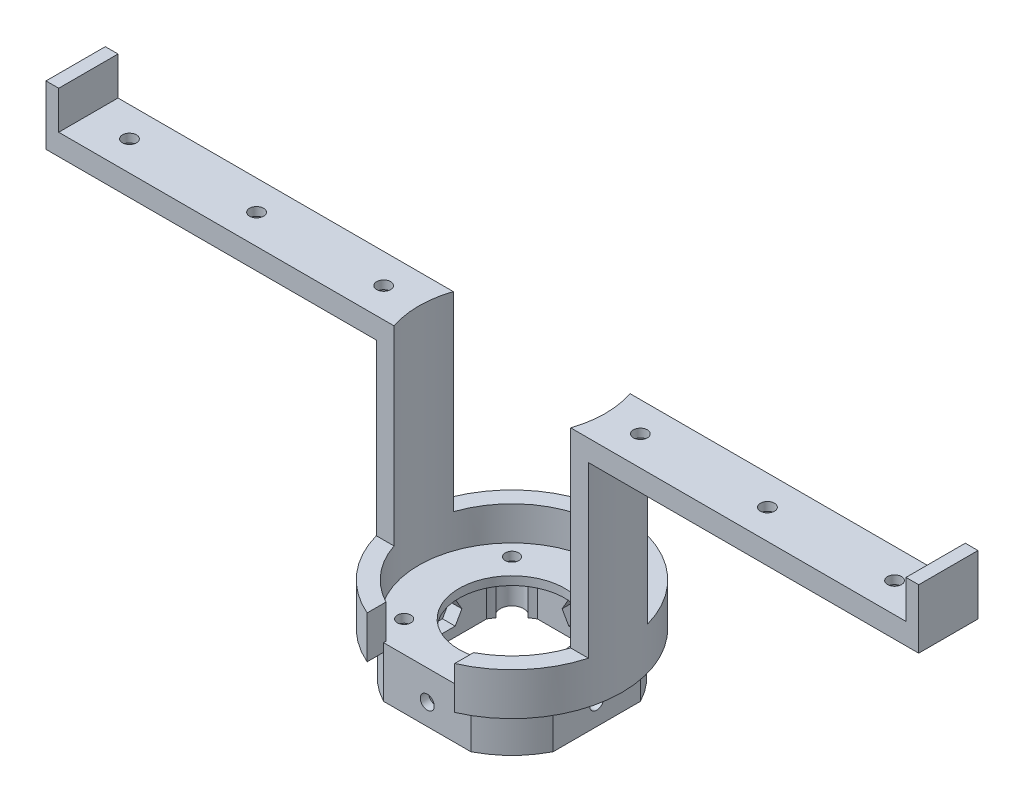
SolidWorks part; units mm, degrees
ref_plane "前视基准面" through (0, 0, 0) normal (0, 0, 1) x (1, 0, 0)
ref_plane "上视基准面" through (0, 0, 0) normal (0, 1, 0) x (1, 0, 0)
ref_plane "右视基准面" through (0, 0, 0) normal (1, 0, 0) x (0, 0, -1)
sketch "草图1" plane through (0, 0, 0) normal (0, 1, 0) x (1, 0, 0)
  line L0 (0, 0) -> (0, 18) construction
  line L1 (0, 0) -> (12.7279, 12.7279) construction
  line L2 (-32.6893, 0) -> (36.6315, 0) construction
  arc A0 (-20.3411, 8.381) -> (20.3411, 8.381) centre (0, 0) ccw
  circle A1 centre (0, 0) radius 18 construction
  circle A2 centre (12.7279, 12.7279) radius 1.6
  circle A3 centre (12.7279, -12.7279) radius 1.6
  circle A4 centre (-12.7279, -12.7279) radius 1.6
  circle A5 centre (-12.7279, 12.7279) radius 1.6
  circle A6 centre (0, 0) radius 22
  arc A7 (20.3411, 8.381) -> (-20.3411, 8.381) centre (0, 0) ccw
  point P16 (0, 0)
  dimension "D1" = 44
  dimension "D2" = 36
  dimension "D3" = 45
  dimension "D4" = 3.2
  dimension "D5" = 4
extrude "凸台-拉伸1" add sketch "草图1" along normal blind 2 contours A0 A6 A2 A3 A4 A5 region at (0, 0, 0)
sketch "草图2" plane through (0, 2, 0) normal (0, 1, 0) x (1, 0, 0)
  circle A1 centre (0, 0) radius 12.5
  dimension "D1" = 25
extrude "切除-拉伸1" cut sketch "草图2" against normal blind 3 contours A1 region at (0, 2, 0)
sketch "草图5" plane through (0, 0, 0) normal (0, 1, 0) x (1, 0, 0)
  line L6 (0, 27.5) -> (0, -27.5) construction
  circle A1 centre (0, 0) radius 22
  circle A3 centre (0, 0) radius 26
  dimension "D3" = 44
  dimension "D1" = 52
extrude "凸台-拉伸3" add sketch "草图5" along normal blind 10
sketch "草图14" plane through (0, 0, 0) normal (0, -1, 0) x (1, 0, 0)
  line L0 (-10.3078, 20) -> (10.3078, 20)
  line L1 (20, 10.3078) -> (20, -10.3078)
  line L2 (-10.3078, -20) -> (10.3078, -20)
  line L3 (-20, -10.3078) -> (-20, 10.3078)
  line L4 (-9.0139, 15) -> (9.0139, 15)
  line L5 (15, 9.0139) -> (15, -9.0139)
  line L6 (-15, 9.0139) -> (-15, -9.0139)
  line L7 (-9.0139, -15) -> (9.0139, -15)
  arc A0 (-10.3078, 20) -> (-20, 10.3078) centre (0, 0) ccw
  arc A1 (20, 10.3078) -> (10.3078, 20) centre (0, 0) ccw
  arc A2 (10.3078, -20) -> (20, -10.3078) centre (0, 0) ccw
  arc A3 (-20, -10.3078) -> (-10.3078, -20) centre (0, 0) ccw
  arc A4 (-15, -9.0139) -> (-14.1106, -10.3508) centre (0, 0) ccw
  arc A5 (-9.0139, 15) -> (-10.3508, 14.1106) centre (0, 0) ccw
  arc A6 (15, 9.0139) -> (14.1106, 10.3508) centre (0, 0) ccw
  arc A7 (9.0139, -15) -> (10.3508, -14.1106) centre (0, 0) ccw
  arc A8 (-10.3508, 14.1106) -> (-14.1106, 10.3508) centre (-12.7279, 12.7279) ccw
  arc A9 (14.1106, 10.3508) -> (10.3508, 14.1106) centre (12.7279, 12.7279) ccw
  arc A10 (-14.1106, -10.3508) -> (-10.3508, -14.1106) centre (-12.7279, -12.7279) ccw
  arc A11 (10.3508, -14.1106) -> (14.1106, -10.3508) centre (12.7279, -12.7279) ccw
  arc A12 (-14.1106, 10.3508) -> (-15, 9.0139) centre (0, 0) ccw
  arc A13 (10.3508, 14.1106) -> (9.0139, 15) centre (0, 0) ccw
  arc A14 (-10.3508, -14.1106) -> (-9.0139, -15) centre (0, 0) ccw
  arc A15 (14.1106, -10.3508) -> (15, -9.0139) centre (0, 0) ccw
  dimension "D1" = 45
  dimension "D6" = 35
  dimension "D11" = 5.5
  dimension "D12" = 5.5
  dimension "D13" = 5.5
  dimension "D14" = 5.5
  dimension "D2" = 20
  dimension "D3" = 20
  dimension "D4" = 20
  dimension "D5" = 20
  dimension "D7" = 5
  dimension "D8" = 5
  dimension "D9" = 5
  dimension "D10" = 5
extrude "凸台-拉伸5" add sketch "草图14" along normal blind 10
sketch "草图15" plane through (-20, 0, 0) normal (-1, 0, 0) x (0, 0, 1)
  line L0 (10.3078, 0) -> (-10.3078, 0) construction
  line L3 (0, 0) -> (0, -10) construction
  line L4 (10.3078, -10) -> (-10.3078, -10) construction
  circle A0 centre (0, -5) radius 1.65
  dimension "D1" = 3.3
  dimension "D2" = 5
extrude "切除-拉伸2" cut sketch "草图15" against normal blind 42
sketch "草图16" plane through (0, 0, -20) normal (0, 0, -1) x (-1, 0, 0)
  line L0 (10.3078, 0) -> (-10.3078, 0) construction
  line L1 (0, 0) -> (0, -10) construction
  line L2 (10.3078, -10) -> (-10.3078, -10) construction
  circle A0 centre (0, -5) radius 1.65
  dimension "D1" = 3.3
  dimension "D2" = 5
extrude "切除-拉伸3" cut sketch "草图16" against normal blind 42
sketch "草图18" plane through (0, 0, 0) normal (0, 0, 1) x (1, 0, 0)
  line L1 (-1.5877, -2.25) -> (-3.1754, -5)
  line L2 (-3.1754, -5) -> (-1.5877, -7.75)
  line L3 (-1.5877, -7.75) -> (1.5877, -7.75)
  line L4 (1.5877, -7.75) -> (3.1754, -5)
  line L5 (3.1754, -5) -> (1.5877, -2.25)
  line L6 (1.5877, -2.25) -> (-1.5877, -2.25)
  circle A0 centre (0, -5) radius 2.75 construction
  dimension "D1" = 5.5
extrude "切除-拉伸4" cut sketch "草图18" against normal mid plane 36
sketch "草图19" plane through (0, 0, 0) normal (1, 0, 0) x (0, 0, -1)
  line L1 (-1.5877, -2.25) -> (-3.1754, -5)
  line L2 (-3.1754, -5) -> (-1.5877, -7.75)
  line L3 (-1.5877, -7.75) -> (1.5877, -7.75)
  line L4 (1.5877, -7.75) -> (3.1754, -5)
  line L5 (3.1754, -5) -> (1.5877, -2.25)
  line L6 (1.5877, -2.25) -> (-1.5877, -2.25)
  circle A0 centre (0, -5) radius 2.75 construction
  dimension "D1" = 5.5
extrude "切除-拉伸5" cut sketch "草图19" against normal mid plane 36
sketch "草图23" plane through (0, 10, 0) normal (0, 1, 0) x (1, 0, 0)
  line L0 (-20.8567, 7) -> (-25.04, 7)
  line L1 (-26, 0) -> (26, 0) construction
  line L2 (-20.8567, -7) -> (-25.04, -7)
  line L3 (20.8567, 7) -> (25.04, 7)
  line L4 (20.8567, -7) -> (25.04, -7)
  circle A0 centre (0, 0) radius 22 construction
  circle A1 centre (0, 0) radius 26 construction
  circle A2 centre (0, 0) radius 26
  circle A3 centre (0, 0) radius 22 construction
  circle A4 centre (0, 0) radius 22
  circle M8 centre (0, 0) radius 26
  circle M9 centre (0, 0) radius 22
  dimension "D1" = 7
  dimension "D2" = 7
  dimension "D3" = 7
extrude "凸台-拉伸6" add sketch "草图23" along normal blind 45 contours L1 A4 L0 M8 | L1 A2 L2 M9 | L1 A2 L3 M9 | L1 A4 L4 M8 region at (-23.6485, 10, -3.526) region at (23.6485, 10, -3.526) region at (-23.6485, 10, 3.526) region at (23.6485, 10, 3.526)
sketch "草图24" plane through (0, 55, 0) normal (0, 1, 0) x (1, 0, 0)
  line L0 (-20.8567, 7) -> (-25.04, 7) construction
  line L1 (-25.04, -7) -> (-75.3, -7)
  line L2 (-25.04, -7) -> (-25.04, 7)
  line L3 (-25.04, 7) -> (-75.3, 7)
  line L4 (-75.3, -7) -> (-75.3, 7)
  dimension "D1" = 50.26
extrude "凸台-拉伸7" add sketch "草图24" against normal blind 5
mirror "镜向1" about plane through (0, 0, 0) normal (1, 0, 0) of "凸台-拉伸7"
sketch "草图25" plane through (0, 55, 0) normal (0, 1, 0) x (1, 0, 0)
  line L0 (-75.3, 7) -> (-75.3, -7) construction
  line L2 (-22, 0) -> (-75.3, 0) construction
  circle A0 centre (-60.3, 0) radius 1.65
  arc A1 (-20.8567, 7) -> (-20.8567, -7) centre (0, 0) ccw construction
  circle A2 centre (-30.3, 0) radius 1.65
  dimension "D1" = 3.3
  dimension "D3" = 3.3
  dimension "D2" = 15
  dimension "D4" = 30
extrude "切除-拉伸6" cut sketch "草图25" against normal blind 5
sketch "草图26" plane through (0, 50, 0) normal (0, 1, 0) x (1, 0, 0)
  line L1 (-58.7123, 2.75) -> (-61.8877, 2.75)
  line L2 (-61.8877, 2.75) -> (-63.4754, 0)
  line L3 (-63.4754, 0) -> (-61.8877, -2.75)
  line L4 (-61.8877, -2.75) -> (-58.7123, -2.75)
  line L5 (-58.7123, -2.75) -> (-57.1245, 0)
  line L6 (-57.1245, 0) -> (-58.7123, 2.75)
  line L7 (-31.8877, 2.75) -> (-33.4754, 0)
  line L8 (-33.4754, 0) -> (-31.8877, -2.75)
  line L9 (-31.8877, -2.75) -> (-28.7123, -2.75)
  line L10 (-28.7123, -2.75) -> (-27.1245, 0)
  line L11 (-27.1245, 0) -> (-28.7123, 2.75)
  line L12 (-28.7123, 2.75) -> (-31.8877, 2.75)
  circle A0 centre (-60.3, 0) radius 2.75 construction
  circle A1 centre (-30.3, 0) radius 2.75 construction
  dimension "D1" = 5.5
  dimension "D2" = 5.5
extrude "切除-拉伸7" cut sketch "草图26" along normal blind 3
mirror "镜向3" about plane through (0, 0, 0) normal (1, 0, 0) of "切除-拉伸6", "切除-拉伸7"
sketch "草图28" plane through (0, 0, 0) normal (0, -1, 0) x (1, 0, 0)
  line L0 (-10.34, 20) -> (10.34, 20)
  line L1 (10.3078, 20) -> (-10.3078, 20) construction
  line L2 (10.34, 20) -> (10.34, 23.8555)
  line L3 (-10.34, 20) -> (-10.34, 23.8555)
  line L4 (0, 26) -> (0, -26) construction
  line L5 (-26, 0) -> (26, 0) construction
  circle A0 centre (0, 0) radius 26 construction
  arc A2 (10.34, 23.8555) -> (-10.34, 23.8555) centre (0, 0) ccw
  point P4 (0, 20)
  dimension "D1" = 20.68
extrude "切除-拉伸9" cut sketch "草图28" against normal blind 10
sketch "草图29" plane through (0, 10, 0) normal (0, 1, 0) x (1, 0, 0)
  line L6 (-10.34, -20) -> (-10.34, -19.4187)
  line L7 (10.34, -20) -> (10.34, -19.4187)
  line L8 (9.1652, -20) -> (10.34, -20) construction
  line L9 (9.1652, -20) -> (10.34, -20)
  line L10 (-10.34, -20) -> (-9.1652, -20) construction
  line L11 (-10.34, -20) -> (-9.1652, -20)
  circle A6 centre (0, 0) radius 22 construction
  circle A7 centre (0, 0) radius 22 construction
  arc A8 (-10.34, -19.4187) -> (-9.1652, -20) centre (0, 0) ccw
  arc A9 (9.1652, -20) -> (10.34, -19.4187) centre (0, 0) ccw
extrude "切除-拉伸10" cut sketch "草图29" against normal blind 8
sketch "草图34" plane through (0, 50, 0) normal (0, -1, 0) x (1, 0, 0)
  line L0 (-75.3, 0) -> (75.3, 0) construction
  line L1 (-75.3, -7) -> (-100, -7)
  line L2 (-75.3, -7) -> (-75.3, 7)
  line L3 (-75.3, 7) -> (-100, 7)
  line L4 (-100, -7) -> (-100, 7)
  line L5 (75.3, -7) -> (100, -7)
  line L6 (75.3, -7) -> (75.3, 7)
  line L7 (75.3, 7) -> (100, 7)
  line L8 (100, -7) -> (100, 7)
  line L9 (-75.3, -7) -> (-75.3, 7) construction
  line L10 (75.3, -7) -> (75.3, 7) construction
  line L12 (-75.3, 7) -> (-25.04, 7) construction
  line L13 (75.3, 7) -> (25.04, 7) construction
  point P14 (-75.3, 0)
  point P17 (75.3, 0)
  dimension "D1" = 24.7
  dimension "D2" = 24.7
extrude "凸台-拉伸9" add sketch "草图34" against normal blind 5
sketch "草图35" plane through (0, 55, 0) normal (0, 1, 0) x (1, 0, 0)
  circle A0 centre (-90.3, 0) radius 1.65
  circle A1 centre (90.3, 0) radius 1.65
  circle A2 centre (-60.3, 0) radius 1.65 construction
  circle A3 centre (60.3, 0) radius 1.65 construction
  dimension "D3" = 3.3
  dimension "D4" = 3.3
  dimension "D1" = 30
  dimension "D2" = 30
extrude "切除-拉伸11" cut sketch "草图35" against normal blind 5
sketch "草图36" plane through (0, 50, 0) normal (0, -1, 0) x (1, 0, 0)
  line L1 (-91.8877, 2.75) -> (-93.4754, 0)
  line L2 (-93.4754, 0) -> (-91.8877, -2.75)
  line L3 (-91.8877, -2.75) -> (-88.7123, -2.75)
  line L4 (-88.7123, -2.75) -> (-87.1245, 0)
  line L5 (-87.1245, 0) -> (-88.7123, 2.75)
  line L6 (-88.7123, 2.75) -> (-91.8877, 2.75)
  line L7 (91.8877, 2.75) -> (88.7123, 2.75)
  line L8 (88.7123, 2.75) -> (87.1245, 0)
  line L9 (87.1245, 0) -> (88.7123, -2.75)
  line L10 (88.7123, -2.75) -> (91.8877, -2.75)
  line L11 (91.8877, -2.75) -> (93.4754, 0)
  line L12 (93.4754, 0) -> (91.8877, 2.75)
  circle A0 centre (-90.3, 0) radius 2.75 construction
  circle A1 centre (90.3, 0) radius 2.75 construction
  dimension "D1" = 5.5
  dimension "D2" = 5.5
extrude "切除-拉伸12" cut sketch "草图36" against normal blind 3
sketch "草图37" plane through (0, 50, 0) normal (0, -1, 0) x (1, 0, 0)
  line L0 (-100, 7) -> (-25.04, 7) construction
  line L1 (-100, -7) -> (-103, -7)
  line L2 (-100, -7) -> (-100, 7)
  line L3 (-100, 7) -> (-103, 7)
  line L4 (-103, -7) -> (-103, 7)
  line L5 (100, 7) -> (25.04, 7) construction
  line L6 (100, -7) -> (103, -7)
  line L7 (100, -7) -> (100, 7)
  line L8 (100, 7) -> (103, 7)
  line L9 (103, -7) -> (103, 7)
  dimension "D1" = 3
  dimension "D2" = 3
extrude "凸台-拉伸10" add sketch "草图37" against normal blind 14
